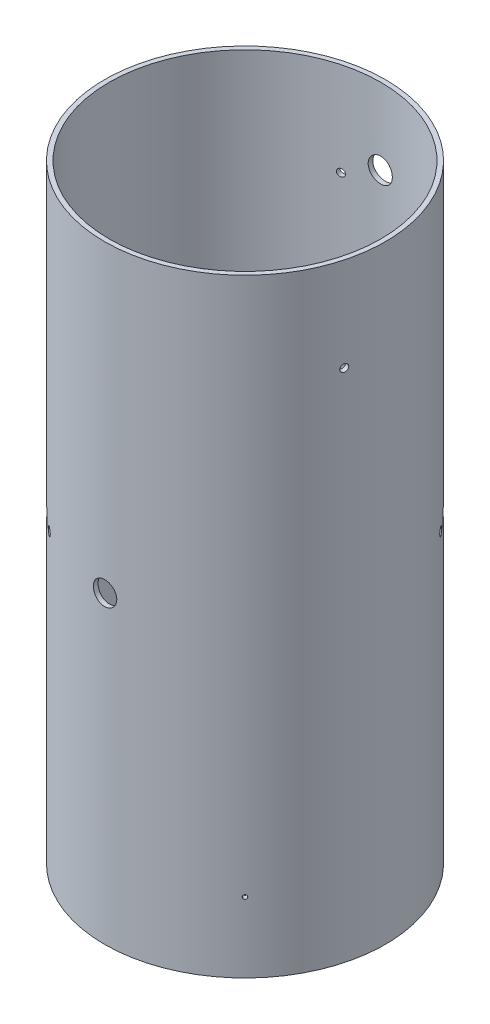
SolidWorks part; units mm, degrees
material "A-Glass Fiber"
ref_plane "Front Plane" through (0, 0, 0) normal (0, 0, 1) x (1, 0, 0)
ref_plane "Top Plane" through (0, 0, 0) normal (0, 1, 0) x (1, 0, 0)
ref_plane "Right Plane" through (0, 0, 0) normal (1, 0, 0) x (0, 0, -1)
sketch "Sketch1" plane through (0, 0, 0) normal (0, 1, 0) x (1, 0, 0)
  circle A0 centre (0, 0) radius 76.1746
  circle A1 centre (0, 0) radius 73.66
  dimension "D1" = 152.3492
  dimension "D2" = 147.32
extrude "Boss-Extrude1" add sketch "Sketch1" along normal blind 330.2
sketch "Sketch4" plane through (0, 0, 0) normal (0, 0, 1) x (1, 0, 0)
  line L0 (-76.1746, 0) -> (76.1746, 0) construction
  line L1 (76.1746, 330.2) -> (-76.1746, 330.2) construction
  line L2 (0, 330.2) -> (0, 0) construction
  line L3 (73.66, 330.2) -> (-73.66, 330.2) construction
  point P0 (0, 41.275)
  point P3 (0, 288.925)
  dimension "D1" = 41.275
  dimension "D2" = 41.275
hole_wizard "1/2 Clearance Hole5" positions "Sketch16" profile "Sketch17" hole size "1/2" standard "ANSI Inch"
sketch "Sketch16" plane through (0, 0, 0) normal (0, 0, 1) x (1, 0, 0)
  point P0 (0, 288.925)
sketch "Sketch17" plane through (0, 288.925, 0) normal (1, 0, 0) x (0, -1, 0)
  line L0 (0, 0) -> (0, 80.1345)
  line L1 (0, 80.1345) -> (6.5481, 76.2)
  line L2 (6.5481, 76.2) -> (6.5481, 0)
  line L5 (6.5481, 0) -> (0, 0)
  line L10 (0, 80.1345) -> (-6.5481, 76.2) construction
  line L11 (0, -6.35) -> (0, 107.95) construction
  dimension "Hole Dia." = 13.0962
  dimension "Hole Depth" = 76.2
  dimension "Drill Angle" = 118
sketch "Sketch27" plane through (0, 0, 0) normal (0, 0, 1) x (1, 0, 0)
  line L0 (0, 330.2) -> (0, 0) construction
  line L1 (-76.1746, 0) -> (76.1746, 0) construction
  circle A0 centre (0, 165.1) radius 6.35
  dimension "D1" = 12.7
  dimension "D2" = 165.1
extrude "Cut-Extrude1" cut sketch "Sketch27" against normal through all both and the other way through all
ref_plane "Plane1" through (0, 0, 0) normal (-0.7071, 0, 0.7071) x (0.7071, 0, 0.7071)
ref_plane "Plane2" through (0, 0, 0) normal (-0.7071, 0, 0.7071) x (0, -1, 0)
sketch "Sketch30" plane through (0, 0, 0) normal (-0.7071, 0, 0.7071) x (0.7071, 0, 0.7071)
  line L0 (0, 330.2) -> (0, 0) construction
  line L1 (4.953, 160.147) -> (-4.953, 160.147)
  line L2 (4.953, 160.147) -> (4.953, 170.053)
  line L3 (4.953, 170.053) -> (-4.953, 170.053)
  line L4 (-4.953, 160.147) -> (-4.953, 170.053)
  line L5 (4.953, 160.147) -> (-4.953, 170.053) construction
  line L6 (4.953, 170.053) -> (-4.953, 160.147) construction
  line L7 (-76.1746, 0) -> (76.1746, 0) construction
  circle A0 centre (-12.7, 165.1) radius 2.1831
  circle A1 centre (12.7, 165.1) radius 2.1831
  point P0 (0, 165.1)
  dimension "D3" = 4.3663
  dimension "D4" = 4.3663
  dimension "D1" = 9.906
  dimension "D2" = 9.906
  dimension "D5" = 12.7
  dimension "D6" = 12.7
  dimension "D7" = 165.1
extrude "Cut-Extrude2" cut sketch "Sketch30" against normal through all both and the other way through all
sketch "Sketch23" plane through (0, 0, 0) normal (-0.7071, 0, 0.7071) x (0.7071, 0, 0.7071)
  line L0 (0, 0) -> (0, 330.2) construction
  line L1 (73.66, 330.2) -> (-73.66, 330.2) construction
  line L2 (-76.1746, 165.1) -> (76.1746, 165.1) construction
  line L3 (76.1746, 0) -> (76.1746, 330.2) construction
  circle A1 centre (0, 38.1) radius 1.0922
  point P12 (0, 165.1)
  dimension "D2" = 127
extrude "Shear Scrrews" cut sketch "Sketch23" against normal through all
pattern_circular "CirPattern1" count 4 over 360 about axis through (0, 330.2, 0) along (0, -1, 0) of "Shear Scrrews"
hole_wizard "Ø4.0 (4) Diameter Hole1" positions "Sketch24" profile "Sketch25" hole size "Ø4.0" standard "ANSI Metric"
sketch "Sketch24" plane through (0, 0, 0) normal (-0.7071, 0, 0.7071) x (0, -1, 0)
  line L0 (-330.2, 76.1746) -> (-330.2, -76.1746) construction
  point P0 (-279.4, 0)
  dimension "D1" = 50.8
sketch "Sketch25" plane through (0, 279.4, 0) normal (0, 1, 0) x (-0.7071, 0, -0.7071)
  line L0 (0, 0) -> (0, 90.1017)
  line L1 (0, 90.1017) -> (2, 88.9)
  line L2 (2, 88.9) -> (2, 0)
  line L5 (2, 0) -> (0, 0)
  line L10 (0, 90.1017) -> (-2, 88.9) construction
  line L11 (0, -6.35) -> (0, 107.95) construction
  dimension "Hole Dia." = 4
  dimension "Hole Depth" = 88.9
  dimension "Drill Angle" = 118
pattern_circular "CirPattern2" count 3 over 360 about axis through (0, 330.2, 0) along (0, 1, 0) of "Ø4.0 (4) Diameter Hole1"
equation "\"Mid_Coupler_Length\" = 13in"
equation "\"D1@Boss-Extrude1\"=\"Mid_Coupler_Length\""
equation "\"Shear_Screw_Coupler_Location\" = 4.5in"
equation "\"Shear_Screw_Diameter\" = 0.086in"
equation "\"D2@Sketch23\"=\"Shear_Screw_Coupler_Location\"+0.5"
equation "\"Mid_Tube_Length\"= 1in"
equation "\"Bodytube_OD\" = 6.17in"
equation "\"Bodytube_ID\" = 5.998in"
equation "\"Camera_Cutout_Width\"=10mm"
equation "\"Camera_Cutout_Height\"=7mm"
equation "\"Fwd_Tube_Length\" = 38.5in"
equation "\"BKHD_Screw_Diam\"= 3.5mm"
equation "\"Fwd_BKHD_From_Top\" = 18in"
equation "\"Motor_OD\" = 4in"
equation "\"Aft_Section_Length\"= 36in"
equation "\"AB_Coupler_OD_Length\"= 1in"
equation "\"AB_Coupling_Section_Length\"= 0.375in"
equation "\"AB_Coupler_Length\"= \"AB_Coupler_OD_Length\" + \"AB_Coupling_Section_Length\" * 2"
equation "\"Cutout_Angle\" = 80"
equation "\"AB_Paddle_Height\" = 0.375in"
equation "\"AB_Coupler_Num_Screws\"= 4"
equation "\"AB_BKHD_Thickness\" = 0.375in"
equation "\"AB_Mount_From_Bottom\" = 23.175in"
equation "\"Num_Cutouts\" = 3"
equation "\"AB_Coupler_OD\"= 6.17in"
equation "\"AB_Coupler_ID\"= 5.75in"
equation "\"AB_Coupler_Surface_Diameter\"= 5.998in"
equation "\"AB_Coupling_Screw_Diameter\"= 0.15748in"
equation "\"AB_Central_Bushing_Length\" = .4724in"
equation "\"Lead_Screw_Dist\" = 3.4in"
equation "\"Lead_Screw_Diam\" = 0.386in"
equation "\"Lead_Screw_Length\" = (\"Mid_Coupler_Length\" + 2*0.375in + 2*.75in)"
equation "\"Paddle_Pin_Offset\" = .25in"
equation "\"Paddle_Pin_Radius\" = 2.25in"
equation "\"SS_Paddle_Pin_Radius\" = 2.25*0.66in"
equation "\"Paddle_Gear_OD\" = 3.2in"
equation "\"Drive_Gear_OD\" = 1.7in"
equation "\"Fin_Thickness\"= .118in"
equation "\"Guiderail_Cutout_Diameter\"= 1.5in"
equation "\"DB9_Hole_Dist\" = 25mm"
equation "\"DB9_Relief_Width\" = 0.47in"
equation "\"DB9_Relief_Hole_Offset\" = 0.09in"
equation "\"Airbrakes_Wire_Hole_Dia\" = .25in"
equation "\"Airbrakes_Wire_Hole_Dist\" = 1.1in"
equation "\"Servo_Gear_Offset\" = 0.5in"
equation "\"FWD_Shear_Screw_Dist\" = 1.5in"
equation "\"Camera_Screw_Dia\" = 0.216535"
equation "\"Camera_Hole_Angle\" = atn ( 2 / 3 * tan ( 12.5deg ) )"
equation "\"D1@Sketch26\"=\"Camera_Cutout_Height\""
equation "\"D2@Sketch26\"=\"Camera_Cutout_Width\""
equation "\"D3@Sketch26\"=6.125"
equation "\"D1@Sketch28\"=\"Camera_Screw_Dia\""
equation "\"D2@CirPattern3\"=\"Camera_Hole_Angle\""
equation "\"D1@Sketch29\"=\"Camera_Screw_Dia\""
equation "\"D2@CirPattern4\"=\"Camera_Hole_Angle\""
equation "\"Coupler_OD\" = 5.998"
equation "\"D1@Sketch1\"=\"Coupler_OD\""
equation "\"Coupler_ID\" = 5.8"
equation "\"D2@Sketch1\"=\"Coupler_ID\""
